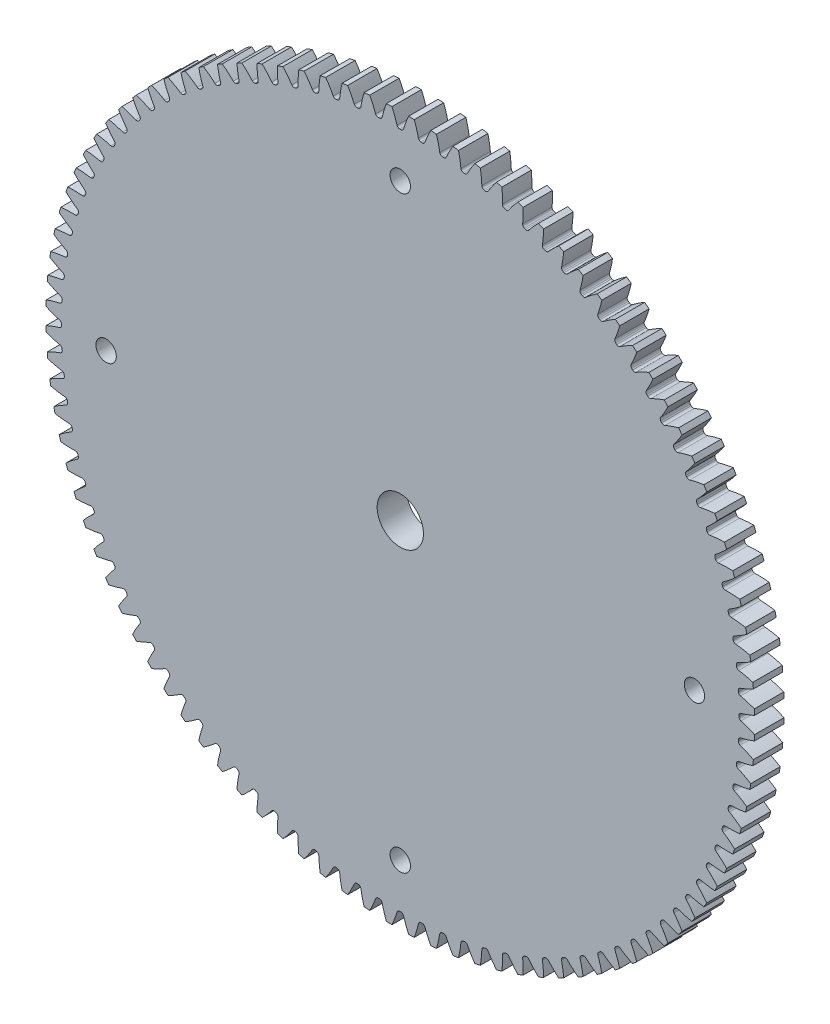
SolidWorks part; units mm, degrees
ref_plane "Front Plane" through (0, 0, 0) normal (0, 0, 1) x (1, 0, 0)
ref_plane "Top Plane" through (0, 0, 0) normal (0, 1, 0) x (1, 0, 0)
ref_plane "Right Plane" through (0, 0, 0) normal (1, 0, 0) x (0, 0, -1)
sketch "Sketch1" plane through (0, 0, 0) normal (0, 0, 1) x (1, 0, 0)
  line L0 (0, 0) -> (0, 75) construction
  line L1 (-24.1045, 83.7733) -> (24.1045, 66.2267) construction
  circle A0 centre (0, 0) radius 73.125 construction
  circle A1 centre (0, 0) radius 76.5 construction
  circle A2 centre (0, 0) radius 75 construction
  circle A3 centre (0, 0) radius 70.4769 construction
  circle A4 centre (0, 0) radius 40 construction
  circle A5 centre (0, 0) radius 7.5 construction
  point P8 (0.75, 0)
  point P13 (50, 0)
  dimension "OD" = 153
  dimension "Root Diameter" = 146.25
  dimension "Gear Pitch Diameter" = 150
  dimension "Base Diameter" = 140.9539
  dimension "Hub Diameter" = 80
  dimension "For Shaft Diameter" = 15
  dimension "Pressure Angle" = 20
  dimension "Number of Teeth" = 100
  dimension "Module" = 1.5
sketch "Sketch2" plane through (0, 0, 0) normal (1, 0, 0) x (0, 0, -1)
  line L0 (-14, 0) -> (6.35, 0) construction
  line L1 (6.35, 76.5) -> (6.35, -76.5) construction
  line L2 (0, -40) -> (-14, -40) construction
  line L3 (-14, 76.5) -> (6.35, 76.5) construction
  line L8 (-14, -40) -> (-14, 40) construction
  point P4 (0, 76.5)
  point P5 (-7, 0)
  dimension "Overall Width" = 20.35
  dimension "Hub Width" = 14
  dimension "Approx Set Screw Positon" = 7
  dimension "Face Width" = 6.35
sketch "Sketch3" plane through (0, 0, 0) normal (0, 0, 1) x (1, 0, 0)
  circle A0 centre (0, 0) radius 76.5
  circle A1 centre (0, 0) radius 76.5 construction
extrude "Boss-Extrude1" add sketch "Sketch3" against normal up to vertex (6.35 mm away) up to point (0, 0, -6.35)
sketch "Sketch4" plane through (0, 0, 0) normal (0, 0, 1) x (1, 0, 0)
  line L0 (73.1226, 0.589) -> (73.1226, -0.589)
  arc A3 (76.4789, 1.7978) -> (76.4789, -1.7978) centre (0, 0) cw
  circle A4 centre (0, 0) radius 76.5 construction
  arc A5 (73.1226, 0.589) -> (76.4789, 1.7978) centre (66.9977, 22.8603) ccw
  circle A8 centre (0, 0) radius 73.125 construction
  arc A9 (73.1226, -0.589) -> (76.4789, -1.7978) centre (66.9977, -22.8603) cw
  spline S0 degree 4 poles (70.4769, 0.0566) (70.4862, 0.0567) (70.5123, 0.0572) (70.5615, 0.0592) (70.6419, 0.0639) (70.7443, 0.072) (70.8767, 0.0848) (71.0327, 0.1031) (71.2042, 0.1265) (71.3909, 0.1556) (71.5772, 0.1877) (71.763, 0.2226) (71.9483, 0.2601) (72.1727, 0.3086) (72.4418, 0.3712) (72.7566, 0.4506) (73.1136, 0.5483) (73.4778, 0.6559) (73.8362, 0.7684) (74.1986, 0.8897) (74.5493, 1.0125) (74.9138, 1.148) (75.2504, 1.277) (75.6277, 1.4303) (75.9323, 1.5566) (76.3344, 1.7325) (76.572, 1.8392) (76.8501, 1.9673) (76.9736, 2.0258) (77.0497, 2.0619) knots 0 0 0 0 0 0.005377 0.015084 0.028532 0.04661 0.064855 0.092111 0.119476 0.146842 0.174209 0.201575 0.228941 0.256307 0.307035 0.361767 0.4165 0.471232 0.525964 0.580697 0.635429 0.690161 0.744894 0.799626 0.854358 0.909091 0.954545 1 1 1 1 1 construction
  spline S1 degree 4 poles (70.4769, 0.0566) (70.4862, 0.0567) (70.5123, 0.0572) (70.5615, 0.0592) (70.6419, 0.0639) (70.7443, 0.072) (70.8767, 0.0848) (71.0327, 0.1031) (71.2042, 0.1265) (71.3909, 0.1556) (71.5772, 0.1877) (71.763, 0.2226) (71.9483, 0.2601) (72.1727, 0.3086) (72.4418, 0.3712) (72.7566, 0.4506) (73.1136, 0.5483) (73.4778, 0.6559) (73.8362, 0.7684) (74.1986, 0.8897) (74.5493, 1.0125) (74.9138, 1.148) (75.2504, 1.277) (75.6277, 1.4303) (75.9323, 1.5566) (76.2472, 1.6943) (76.4005, 1.7625) (76.4789, 1.7978) knots 0 0 0 0 0 0.005377 0.015084 0.028532 0.04661 0.064855 0.092111 0.119476 0.146842 0.174209 0.201575 0.228941 0.256307 0.307035 0.361767 0.4165 0.471232 0.525964 0.580697 0.635429 0.690161 0.744894 0.799626 0.854358 0.909091 0.909091 0.909091 0.909091 0.909091 construction
  spline S2 degree 4 poles (70.4769, -0.0566) (70.4862, -0.0567) (70.5123, -0.0572) (70.5615, -0.0592) (70.6419, -0.0639) (70.7443, -0.072) (70.8767, -0.0848) (71.0327, -0.1031) (71.2042, -0.1265) (71.3909, -0.1556) (71.5772, -0.1877) (71.763, -0.2226) (71.9483, -0.2601) (72.1727, -0.3086) (72.4418, -0.3712) (72.7566, -0.4506) (73.1136, -0.5483) (73.4778, -0.6559) (73.8362, -0.7684) (74.1986, -0.8897) (74.5493, -1.0125) (74.9138, -1.148) (75.2504, -1.277) (75.6277, -1.4303) (75.9323, -1.5566) (76.3344, -1.7325) (76.572, -1.8392) (76.8501, -1.9673) (76.9736, -2.0258) (77.0497, -2.0619) knots 0 0 0 0 0 0.005377 0.015084 0.028532 0.04661 0.064855 0.092111 0.119476 0.146842 0.174209 0.201575 0.228941 0.256307 0.307035 0.361767 0.4165 0.471232 0.525964 0.580697 0.635429 0.690161 0.744894 0.799626 0.854358 0.909091 0.954545 1 1 1 1 1 construction
  spline S3 degree 4 poles (70.4769, -0.0566) (70.4862, -0.0567) (70.5123, -0.0572) (70.5615, -0.0592) (70.6419, -0.0639) (70.7443, -0.072) (70.8767, -0.0848) (71.0327, -0.1031) (71.2042, -0.1265) (71.3909, -0.1556) (71.5772, -0.1877) (71.763, -0.2226) (71.9483, -0.2601) (72.1727, -0.3086) (72.4418, -0.3712) (72.7566, -0.4506) (73.1136, -0.5483) (73.4778, -0.6559) (73.8362, -0.7684) (74.1986, -0.8897) (74.5493, -1.0125) (74.9138, -1.148) (75.2504, -1.277) (75.6277, -1.4303) (75.9323, -1.5566) (76.2472, -1.6943) (76.4005, -1.7625) (76.4789, -1.7978) knots 0 0 0 0 0 0.005377 0.015084 0.028532 0.04661 0.064855 0.092111 0.119476 0.146842 0.174209 0.201575 0.228941 0.256307 0.307035 0.361767 0.4165 0.471232 0.525964 0.580697 0.635429 0.690161 0.744894 0.799626 0.854358 0.909091 0.909091 0.909091 0.909091 0.909091 construction
  dimension "D1" = 1.1781
extrude "Cut-Extrude1" cut sketch "Sketch4" against normal through all both and the other way through all
fillet "Fillet1" radius 0.589 2 edges at (73.1226, 0.589, -3.175) (73.1226, -0.589, -3.175)
pattern_circular "CirPattern1" count 100 over 360 about axis through (0, 0, 14) along (0, 0, -1) of "Cut-Extrude1", "Fillet1"
sketch "Sketch5" plane through (0, 0, -6.35) normal (0, 0, -1) x (-1, 0, 0)
  circle A0 centre (0, 0) radius 5
  dimension "D1" = 10
extrude "Cut-Extrude2" cut sketch "Sketch5" against normal through all
sketch "Sketch6" plane through (0, 0, -6.35) normal (0, 0, -1) x (-1, 0, 0)
  circle A0 centre (63.5, 0) radius 2.2
  circle A1 centre (0, -63.5) radius 2.2
  circle A2 centre (-63.5, 0) radius 2.2
  circle A3 centre (0, 63.5) radius 2.2
  point P11 (0, 0)
  dimension "D1" = 4.4
  dimension "D3" = 127
  dimension "D2" = 4
extrude "Cut-Extrude3" cut sketch "Sketch6" against normal through all
sketch "Sketch7" plane through (0, 0, 0) normal (0, 0, 1) x (1, 0, 0)
  circle A0 centre (0, 0) radius 75 construction
  dimension "D1" = 150
sketch "Sketch8" plane through (0, 0, 0) normal (0, 1, 0) x (1, 0, 0)
  line L0 (0, 0) -> (0, 8.1709) construction
  line L1 (-75, 0) -> (75, 0) construction
equation "\"Number of Teeth\"= 100"
equation "\"Module\"= 1.5"
equation "\"Diametral Pitch\"= 1 / \"Module\""
equation "\"Dedendum\"= 1.25 / \"Diametral Pitch\""
equation "\"Pitch Diameter\"= \"Module\" * \"Number of Teeth\""
equation "\"Root Diameter\"= \"Pitch Diameter\" - ( 2 * \"Dedendum\" )"
equation "\"Root Diameter@Sketch1\"=\"Root Diameter\""
equation "\"OD@Sketch1\" = \"Outside Diameter\""
equation "\"D1@CirPattern1\"=\"Number of Teeth\""
equation "\"Pressure Angle\"=20"
equation "\"Base Diameter\"= \"Pitch Diameter\" * cos ( \"Pressure Angle\" )"
equation "\"Outside Diameter\"= ( \"Number of Teeth\" + 2 ) / \"Diametral Pitch\""
equation "\"Pitch Angle\"= 360deg / \"Number of Teeth\""
equation "\"Alpha\"= sqr ( \"Pitch Diameter\" ^ 2 - \"Base Diameter\" ^ 2 ) / \"Base Diameter\" * 180 / PI - \"Pressure Angle\""
equation "\"Beta\"= ( \"Pitch Angle\" / 4 - \"Alpha\" )"
equation "\"Phi\"= sqr ( ( \"Outside Diameter\" / 2 ) ^ 2 - ( \"Base Diameter\" / 2 ) ^ 2 ) / ( \"Base Diameter\" / 2 )"
equation "\"Addendum\"= 1 / \"Diametral Pitch\""
equation "\"WorkingDepth\"= 2 / \"Diametral Pitch\""
equation "\"WholeDepth\"= 2.25 / \"Diametral Pitch\""
equation "\"Clearance\"= 0.25 / \"Diametral Pitch\""
equation "\"ToothThickness\"= ( pi * 2 ) / \"Diametral Pitch\""
equation "\"CircularPitch\"= pi / \"Diametral Pitch\""
equation "\"Number of Teeth@Sketch1\"=\"Number of Teeth\""
equation "\"Module@Sketch1\"=\"Module\""
equation "\"Pressure Angle@Sketch1\"=\"Pressure Angle\""
equation "\"Gear Pitch Diameter@Sketch1\"=\"Pitch Diameter\""
equation "\"Base Diameter@Sketch1\"=\"Base Diameter\""
equation "\"Fillet\"= \"Clearance\" * cos ( \"Pressure Angle\" ) * tan ( ( 90 + \"Pressure Angle\" ) / 2 )"
equation "\"D1\"= \"Fillet\""
equation "\"Approx Set Screw Positon@Sketch2\" = \"Hub Width@Sketch2\" / 2"
equation "\"D2\"= \"Fillet\" * 2"
equation "\"D1@Sketch4\"=\"CircularPitch\"*0.25"
equation "\"D1@Fillet1\"=\"CircularPitch\"*0.125"
equation "\"Overall Width@Sketch2\"=14+0.25in"
equation "\"D3@Sketch6\"=5in"
